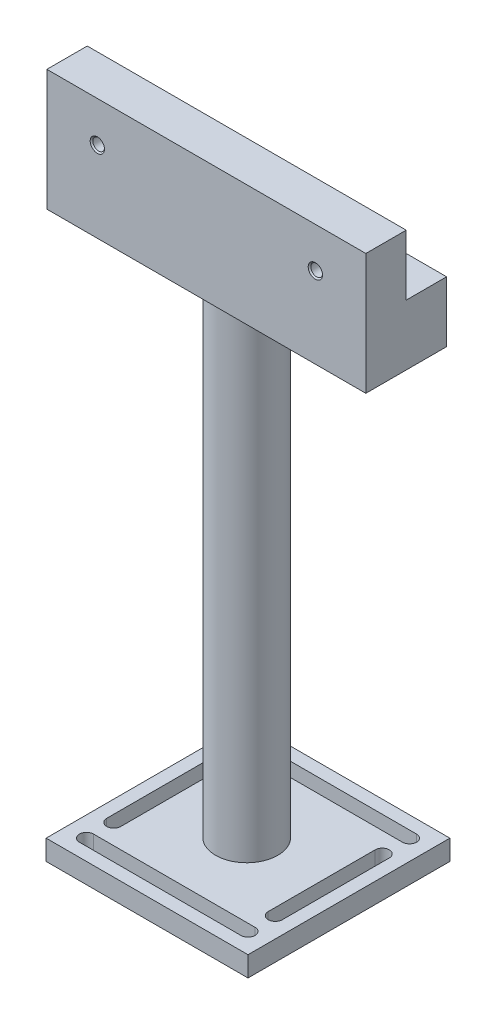
SolidWorks part; units mm, degrees
ref_plane "前视基准面" through (0, 0, 0) normal (0, 0, 1) x (1, 0, 0)
ref_plane "上视基准面" through (0, 0, 0) normal (0, 1, 0) x (1, 0, 0)
ref_plane "右视基准面" through (0, 0, 0) normal (1, 0, 0) x (0, 0, -1)
other "Configuration Table"
sketch "草图1" plane through (0, 0, 0) normal (0, 0, 1) x (1, 0, 0)
  line L0 (0, 30) -> (0, 20) construction
  line L1 (0, 0) -> (79, 0)
  line L2 (0, 0) -> (0, 30)
  line L3 (0, 30) -> (79, 30)
  line L4 (79, 0) -> (79, 30)
  line L5 (0, 20) -> (12.5, 20) construction
  line L6 (39.5, 30) -> (39.5, 0) construction
  dimension "D4" = 30
  dimension "D1" = 79
  dimension "D2" = 10
  dimension "D3" = 12.5
extrude "凸台-拉伸2" add sketch "草图1" along normal blind 10 contours L3 L4 L1 L2
sketch "草图3" plane through (0, 0, 10) normal (0, 0, 1) x (1, 0, 0)
  line L0 (0, 30) -> (12.5, 30) construction
  line L1 (0, 30) -> (79, 30) construction
  line L2 (12.5, 30) -> (12.5, 20) construction
  line L3 (39.5, 30) -> (39.5, 0) construction
  line L4 (0, 0) -> (79, 0) construction
  circle A0 centre (12.5, 20) radius 1.75
  circle A1 centre (66.5, 20) radius 1.75
  point P5 (12.5, 20)
  point P11 (66.5, 20)
  point P19 (12.5, 20)
  dimension "D1" = 12.5
  dimension "D2" = 10
hole_wizard "M3.5 螺纹孔3" positions "草图3" profile "草图8" tap size "M3.5" standard "GB" end condition through all
sketch "草图8" plane through (12.5, 20, 10) normal (1, 0, 0) x (0, -1, 0)
  line L0 (0, 0) -> (0, 10)
  line L1 (0, 10) -> (1.45, 10)
  line L2 (1.45, 10) -> (1.45, 0.325)
  line L3 (1.45, 0.325) -> (1.775, 0)
  line L5 (1.775, 0) -> (0, 0)
  line L6 (-1.45, 0.325) -> (-1.775, 0) construction
  line L11 (0, -6.35) -> (0, 107.95) construction
  dimension "通孔螺纹孔钻头直径" = 2.9
  dimension "通孔螺纹孔钻头深度" = 10
  dimension "近端锥形沉头孔直径" = 3.55
  dimension "近端锥形沉头孔角度" = 90
cosmetic thread "孔螺蚊线4" parameters "D2"=3.5
cosmetic thread "孔螺蚊线5" parameters "D2"=3.5
sketch "草图9" plane through (0, 0, 0) normal (0, 0, -1) x (-1, 0, 0)
  line L0 (-79, 0) -> (-79, 30) construction
  line L1 (-79, 15) -> (0, 15)
  line L2 (-79, 15) -> (-79, 0)
  line L3 (-79, 0) -> (0, 0)
  line L4 (0, 15) -> (0, 0)
extrude "凸台-拉伸3" add sketch "草图9" along normal blind 10
sketch "草图10" plane through (0, 0, 0) normal (0, -1, 0) x (1, 0, 0)
  line L0 (0, 0) -> (79, 0) construction
  line L1 (0, 10) -> (0, -10) construction
  line L2 (79, 10) -> (79, -10) construction
  line L3 (39.5, 10) -> (39.5, -10) construction
  line L4 (0, 10) -> (79, 10) construction
  line L5 (79, -10) -> (0, -10) construction
  circle A0 centre (39.5, 0) radius 7.7017
extrude "凸台-拉伸4" add sketch "草图10" along normal blind 120
sketch "草图11" plane through (0, -120, 0) normal (0, -1, 0) x (1, 0, 0)
  line L0 (39.8135, 0) -> (39.8135, 25) construction
  line L1 (39.8135, 25) -> (14.8135, 25) construction
  line L3 (14.8135, 25) -> (64.8135, 25)
  line L4 (14.8135, 25) -> (14.8135, -25)
  line L5 (14.8135, -25) -> (64.8135, -25)
  line L6 (64.8135, 25) -> (64.8135, -25)
  point P6 (-18.391, 7.7874)
  dimension "D1" = 25
  dimension "D2" = 25
  dimension "D3" = 50
  dimension "D4" = 50
extrude "凸台-拉伸5" add sketch "草图11" along normal blind 5 contours L3 L6 L5 L4
sketch "草图12" plane through (0, -125, 0) normal (0, -1, 0) x (1, 0, 0)
  line L0 (14.8135, 25) -> (14.8135, 20) construction
  line L1 (14.8135, 25) -> (14.8135, -25) construction
  line L2 (14.8135, 20) -> (19.8135, 20) construction
  line L3 (64.8135, 20) -> (59.8135, 20) construction
  line L4 (64.8135, 25) -> (64.8135, -25) construction
  line L5 (19.8135, 20) -> (59.8135, 20) construction
  line L6 (19.8135, 21.75) -> (59.8135, 21.75)
  line L7 (19.8135, 18.25) -> (59.8135, 18.25)
  line L8 (14.8135, 0) -> (64.8135, 0) construction
  line L9 (19.8135, -20) -> (59.8135, -20) construction
  line L10 (19.8135, -21.75) -> (59.8135, -21.75)
  line L11 (19.8135, -18.25) -> (59.8135, -18.25)
  line L12 (19.8135, 18.25) -> (19.8135, 13.25) construction
  line L13 (19.8135, -18.25) -> (19.8135, -13.25) construction
  line L14 (19.8135, 13.25) -> (19.8135, -13.25) construction
  line L15 (21.5635, 13.25) -> (21.5635, -13.25)
  line L16 (18.0635, 13.25) -> (18.0635, -13.25)
  line L17 (39.8135, 25) -> (39.8135, -25) construction
  line L18 (14.8135, 25) -> (64.8135, 25) construction
  line L19 (14.8135, -25) -> (64.8135, -25) construction
  line L20 (59.8135, 13.25) -> (59.8135, -13.25) construction
  line L21 (58.0635, 13.25) -> (58.0635, -13.25)
  line L22 (61.5635, 13.25) -> (61.5635, -13.25)
  arc A0 (19.8135, 21.75) -> (19.8135, 18.25) centre (19.8135, 20) ccw
  arc A1 (59.8135, 18.25) -> (59.8135, 21.75) centre (59.8135, 20) ccw
  arc A2 (19.8135, -21.75) -> (19.8135, -18.25) centre (19.8135, -20) cw
  arc A3 (59.8135, -18.25) -> (59.8135, -21.75) centre (59.8135, -20) cw
  arc A4 (21.5635, 13.25) -> (18.0635, 13.25) centre (19.8135, 13.25) ccw
  arc A5 (18.0635, -13.25) -> (21.5635, -13.25) centre (19.8135, -13.25) ccw
  arc A6 (58.0635, 13.25) -> (61.5635, 13.25) centre (59.8135, 13.25) cw
  arc A7 (61.5635, -13.25) -> (58.0635, -13.25) centre (59.8135, -13.25) cw
  point P10 (39.8135, 20)
  point P20 (39.8135, -20)
  point P29 (19.8135, 0)
  point P42 (59.8135, 0)
  point P47 (0, 0)
  point P48 (0, 0)
  point P49 (0, 0)
  dimension "D4" = 5
  dimension "D1" = 5
  dimension "D2" = 5
  dimension "D3" = 5
  dimension "D5" = 5
extrude "切除-拉伸2" cut sketch "草图12" against normal blind 40 contours L7 A1 L6 A0
extrude "切除-拉伸3" cut sketch "草图12<3>" against normal blind 40
sketch "草图12<3>" plane through (0, -125, 0) normal (0, -1, 0) x (1, 0, 0) same geometry as "草图12"
fillet "圆角3" radius 1 16 edges at (59.8135, -125, 15) (61.5635, -125, 0) (59.8135, -125, -15) (19.8135, -125, -15) (18.0635, -125, 0) (19.8135, -125, 15) (18.0635, -125, 20) (39.8135, -125, 21.75) (61.5635, -125, 20) (58.0635, -125, 0) (21.5635, -125, 0) (39.8135, -125, 18.25) (18.0635, -125, -20) (39.8135, -125, -18.25) (61.5635, -125, -20) (39.8135, -125, -21.75)
